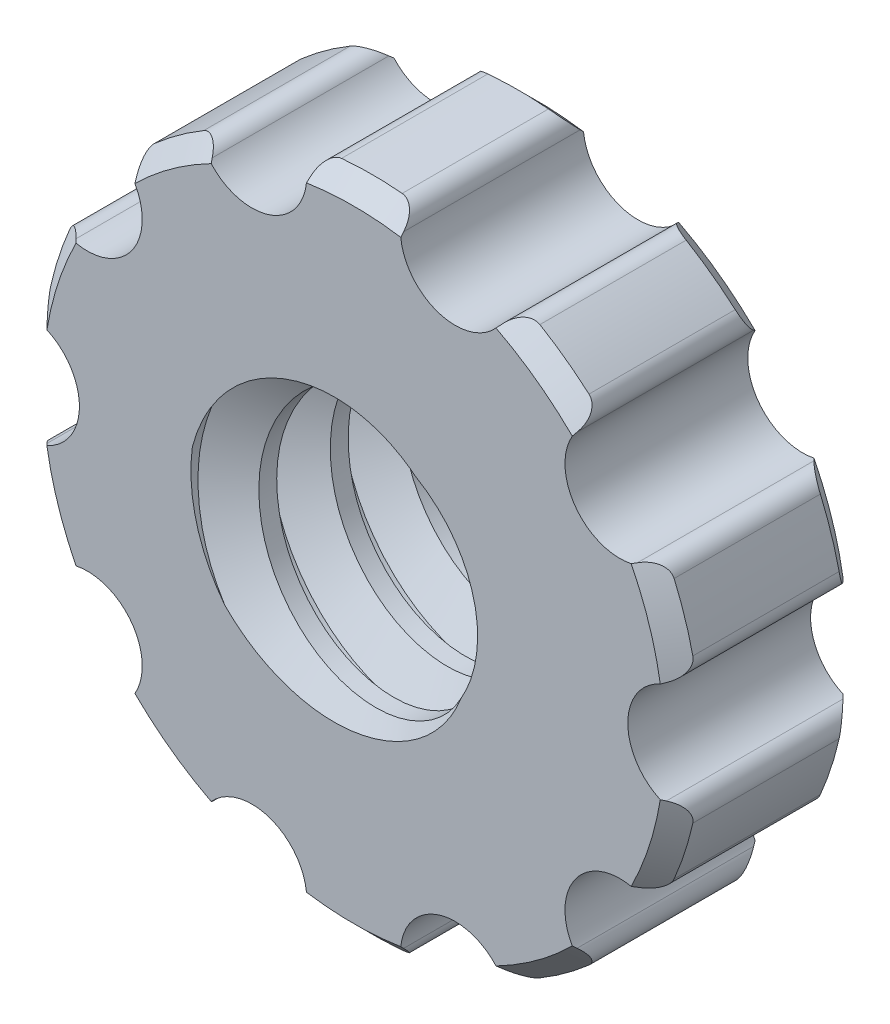
SolidWorks part; units mm, degrees
ref_plane "Front" through (0, 0, 0) normal (0, 0, 1) x (1, 0, 0)
ref_plane "Top" through (0, 0, 0) normal (0, 1, 0) x (1, 0, 0)
ref_plane "Right" through (0, 0, 0) normal (1, 0, 0) x (0, 0, -1)
sketch "Sketch1" plane through (0, 0, 0) normal (0, 0, 1) x (1, 0, 0)
  circle A0 centre (0, 0) radius 9
  circle A1 centre (0, 0) radius 4.45
  dimension "D1" = 8.9
  dimension "D2" = 18
extrude "Boss-Extrude1" add sketch "Sketch1" along normal blind 5
thread "Thread1" pitch 1.9538 method extrude profile "Thread Profile1" start angle 0, offset 1.75, length 0, pitch 1.9538, diameter 8.9
ref_plane "Plane1" through (-4.45, 0, 6.75) normal (0, -1, 0) x (-1, 0, 0)
sketch "Thread Profile1" plane through (-4.45, 0, 6.75) normal (0, -1, 0) x (-1, 0, 0)
  line L0 (0, 0) -> (0, 1.9538) construction
  line L11 (0, 0) -> (0, 1.7096)
  line L12 (0, 1.7096) -> (-1.0576, 1.099)
  line L13 (-1.0576, 1.099) -> (-1.0576, 0.6106)
  line L15 (-1.0576, 0.6106) -> (0, 0)
  line L17 (-1.0576, 0.8548) -> (0, 0.8548) construction
  point P2 (0, 0)
  dimension "Pitch" = 1.9538
  dimension "Profile_Angle" = 60
  dimension "Profile_Land" = 0.4885
  dimension "Profile_Height" = 1.0576
sketch "Sketch4" plane through (0, 0, 0) normal (0, 0, -1) x (-1, 0, 0)
  circle A0 centre (0, 0) radius 9.4647
extrude "Cut-Extrude1" cut sketch "Sketch4" along normal blind 6
sketch "Sketch5" plane through (0, 0, 5) normal (0, 0, 1) x (1, 0, 0)
  circle A0 centre (0, 0) radius 9.4647
extrude "Cut-Extrude2" cut sketch "Sketch5" along normal blind 6
chamfer "Chamfer1" distance 0.5 angle 45 2 edges at (9, 0, 5) (9, 0, 0)
sketch "Sketch6" plane through (0, 0, 5) normal (0, 0, 1) x (1, 0, 0)
  circle A0 centre (-9, 0) radius 1.5
  circle A1 centre (0, 0) radius 9 construction
  dimension "D1" = 3
extrude "Cut-Extrude3" cut sketch "Sketch6" against normal through all
fillet "Fillet1" radius 0.5 2 edges at (-8.875, -1.4948, 2.5) (-8.875, 1.4948, 2.5)
pattern_circular "CirPattern1" count 10 over 360 about axis through (0, 0, 5) along (0, 0, -1) of "Cut-Extrude3", "Fillet1"
